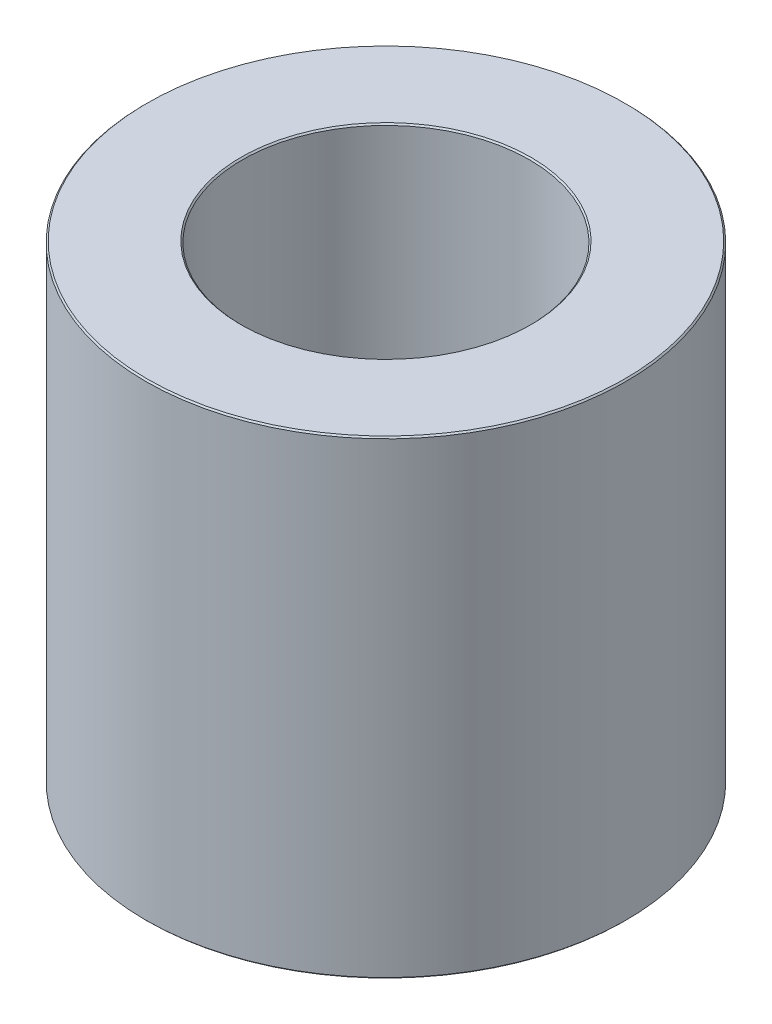
SolidWorks part; units mm, degrees
ref_plane "Front Plane" through (0, 0, 0) normal (0, 0, 1) x (1, 0, 0)
ref_plane "Top Plane" through (0, 0, 0) normal (0, 1, 0) x (1, 0, 0)
ref_plane "Right Plane" through (0, 0, 0) normal (1, 0, 0) x (0, 0, -1)
sketch "Sketch1" plane through (0, 0, 0) normal (0, 1, 0) x (1, 0, 0)
  circle A0 centre (0, 0) radius 40
  dimension "SLEEVE_OD" = 80
extrude "Boss-Extrude1" add sketch "Sketch1" along normal blind 78.1451
sketch "Sketch2" plane through (0, 0, 0) normal (0, 1, 0) x (1, 0, 0)
  circle A0 centre (0, 0) radius 23.9073
  dimension "BORE_D" = 47.8147
extrude "Cut-Extrude1" cut sketch "Sketch2" along normal through all
chamfer "Chamfer1" distance 0.2391 angle 45 4 edges at (0, 78.1451, 23.9073) (0, 0, 23.9073) (0, 0, 40) (0, 78.1451, 40)
